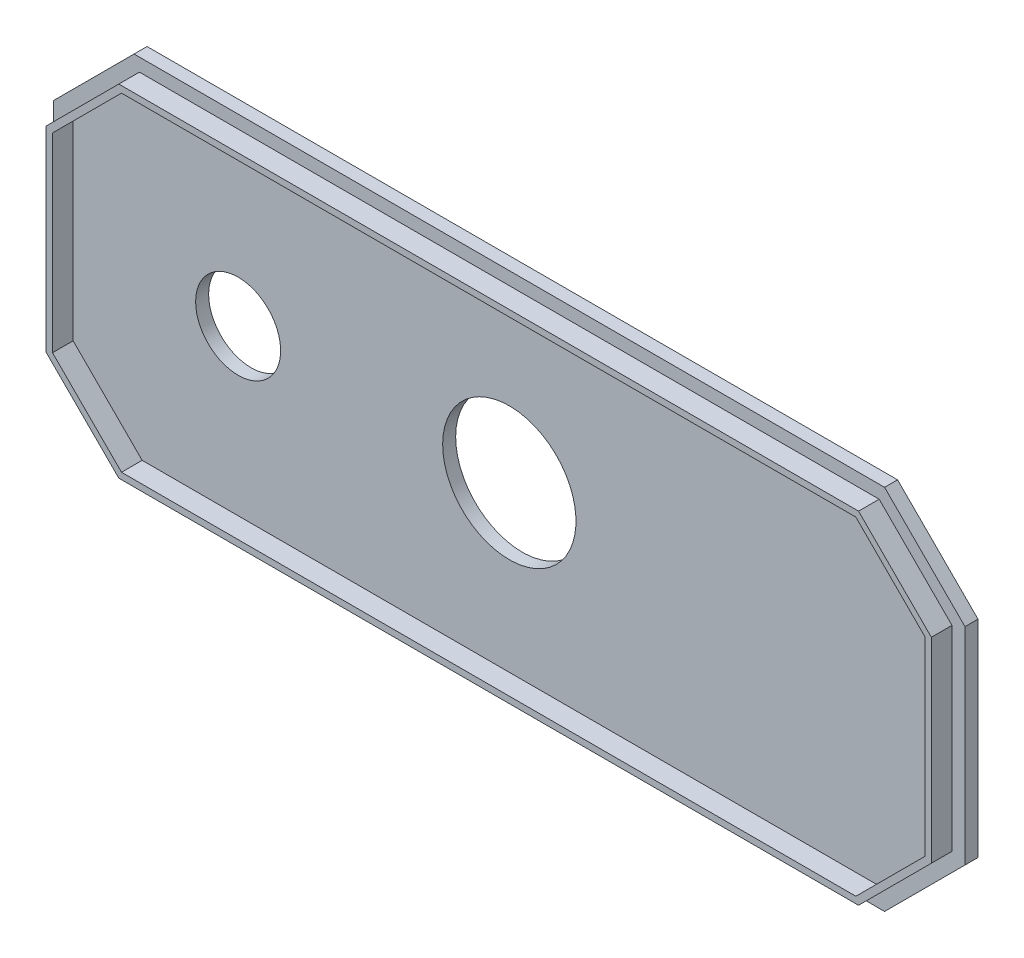
SolidWorks part; units mm, degrees
ref_plane "Front Plane" through (0, 0, 0) normal (0, 0, 1) x (1, 0, 0)
ref_plane "Top Plane" through (0, 0, 0) normal (0, 1, 0) x (1, 0, 0)
ref_plane "Right Plane" through (0, 0, 0) normal (1, 0, 0) x (0, 0, -1)
sketch "Sketch1" plane through (0, 0, 0) normal (0, 0, 1) x (1, 0, 0)
  line L1 (-28.0415, -11.3029) -> (28.0415, -11.3029)
  line L2 (-28.0415, -11.3029) -> (-28.0415, 11.3029)
  line L3 (-28.0415, 11.3029) -> (28.0415, 11.3029)
  line L4 (28.0415, -11.3029) -> (28.0415, 11.3029)
  line L5 (-28.0415, -11.3029) -> (28.0415, 11.3029) construction
  line L6 (-28.0415, 11.3029) -> (28.0415, -11.3029) construction
  point P0 (0, 0)
  dimension "D1" = 56.083
  dimension "D2" = 22.6058
extrude "Boss-Extrude1" add sketch "Sketch1" along normal blind 0.8
sketch "Sketch2" plane through (0, 0, 0.8) normal (0, 0, 1) x (1, 0, 0)
  line L0 (-28.0415, -6.3532) -> (-23.0918, -11.3029)
  line L1 (-28.0415, 11.3029) -> (-28.0415, -11.3029) construction
  line L2 (-28.0415, 6.3532) -> (-23.0918, 11.3029)
  line L3 (28.0415, 11.3029) -> (-28.0415, 11.3029) construction
  line L4 (-23.0918, 11.3029) -> (-28.0415, 11.3029)
  line L5 (-28.0415, 11.3029) -> (-28.0415, 6.3532)
  line L6 (-28.0415, -11.3029) -> (28.0415, -11.3029) construction
  line L7 (-23.0918, -11.3029) -> (-28.0415, -11.3029)
  line L8 (-28.0415, -11.3029) -> (-28.0415, -6.3532)
  line L9 (23.0918, -11.3029) -> (28.0415, -6.3532)
  line L10 (28.0415, -11.3029) -> (28.0415, 11.3029) construction
  line L11 (28.0415, -6.3532) -> (28.0415, -11.3029)
  line L12 (28.0415, -11.3029) -> (23.0918, -11.3029)
  line L13 (23.0918, 11.3029) -> (28.0415, 6.3532)
  line L14 (28.0415, 6.3532) -> (28.0415, 11.3029)
  line L15 (28.0415, 11.3029) -> (23.0918, 11.3029)
  dimension "D1" = 7
  dimension "D2" = 7
  dimension "D3" = 7
  dimension "D4" = 7
  dimension "D5" = 45
  dimension "D6" = 45
  dimension "D7" = 45
  dimension "D8" = 45
extrude "Cut-Extrude1" cut sketch "Sketch2" against normal through all
sketch "Sketch3" plane through (0, 0, 0.8) normal (0, 0, 1) x (1, 0, 0)
  line L0 (22.7604, 10.5029) -> (-22.7604, 10.5029)
  line L1 (-22.7604, 10.5029) -> (-27.2415, 6.0218)
  line L2 (-27.2415, 6.0218) -> (-27.2415, -6.0218)
  line L3 (-27.2415, -6.0218) -> (-22.7604, -10.5029)
  line L4 (-22.7604, -10.5029) -> (22.7604, -10.5029)
  line L5 (22.7604, -10.5029) -> (27.2415, -6.0218)
  line L6 (27.2415, -6.0218) -> (27.2415, 6.0218)
  line L7 (27.2415, 6.0218) -> (22.7604, 10.5029)
  line L48 (-22.5947, 10.1029) -> (-26.8415, 5.8561)
  line L49 (-26.8415, 5.8561) -> (-26.8415, -5.8561)
  line L50 (-26.8415, -5.8561) -> (-22.5947, -10.1029)
  line L51 (-22.5947, -10.1029) -> (22.5947, -10.1029)
  line L52 (22.5947, -10.1029) -> (26.8415, -5.8561)
  line L53 (26.8415, -5.8561) -> (26.8415, 5.8561)
  line L54 (26.8415, 5.8561) -> (22.5947, 10.1029)
  line L55 (22.5947, 10.1029) -> (-22.5947, 10.1029)
  line L56 (-22.5947, 10.1029) -> (-26.8415, 5.8561)
  line L57 (-26.8415, 5.8561) -> (-26.8415, -5.8561)
  line L58 (-26.8415, -5.8561) -> (-22.5947, -10.1029)
  line L59 (-22.5947, -10.1029) -> (22.5947, -10.1029)
  line L60 (22.5947, -10.1029) -> (26.8415, -5.8561)
  line L61 (26.8415, -5.8561) -> (26.8415, 5.8561)
  line L62 (26.8415, 5.8561) -> (22.5947, 10.1029)
  line L63 (22.5947, 10.1029) -> (-22.5947, 10.1029)
  dimension "D1" = 1.2
  dimension "D2" = 0.4
extrude "Boss-Extrude2" add sketch "Sketch3" along normal blind 1.27
sketch "Sketch4" plane through (0, 0, 0) normal (0, 0, -1) x (-1, 0, 0)
  line L0 (16.6877, 0) -> (0, 0) construction
  line L1 (28.0415, 6.3532) -> (28.0415, -6.3532) construction
  circle A0 centre (16.6877, 0) radius 2.6162
  dimension "D1" = 5.2324
  dimension "D2" = 11.3538
extrude "Cut-Extrude2" cut sketch "Sketch4" against normal blind 2.54
sketch "Sketch5" plane through (0, 0, 0) normal (0, 0, -1) x (-1, 0, 0)
  circle A0 centre (0, 0) radius 4.1021
  dimension "D1" = 8.2042
extrude "Cut-Extrude3" cut sketch "Sketch5" against normal blind 2.54
